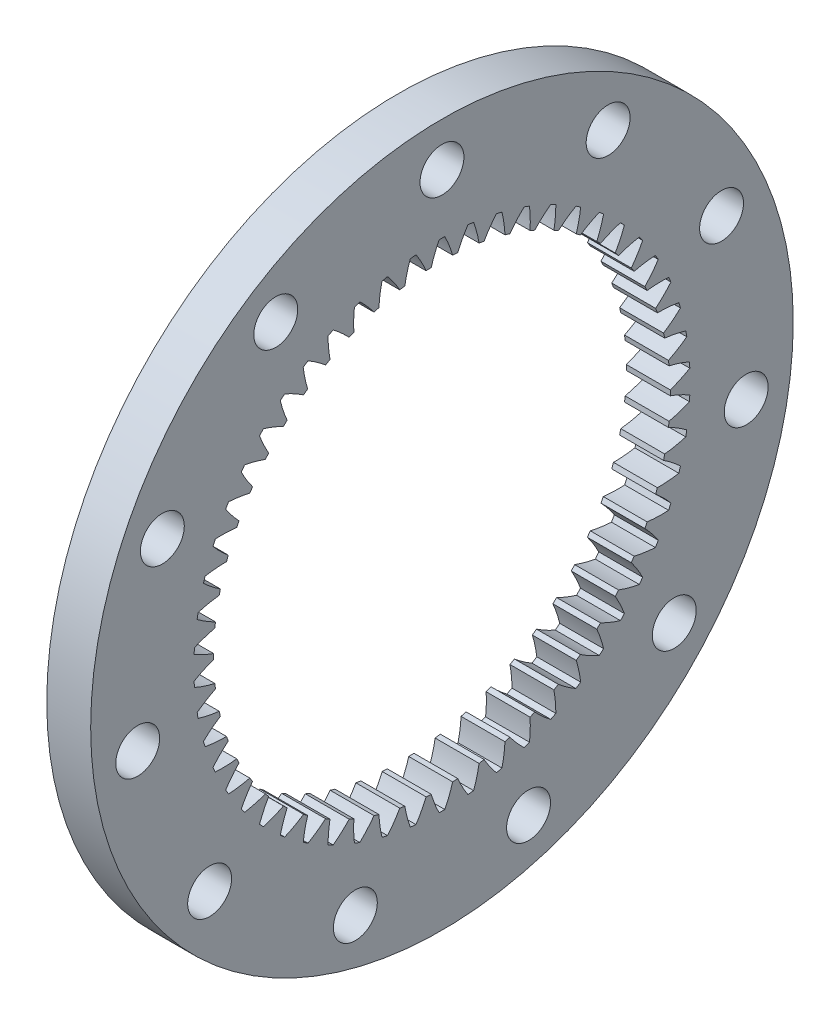
SolidWorks part; units mm, degrees
material "Nylon 101"
ref_plane "Plane1" through (0, 0, 0) normal (0, 0, 1) x (1, 0, 0)
ref_plane "Plane2" through (0, 0, 0) normal (0, 1, 0) x (1, 0, 0)
ref_plane "Plane3" through (0, 0, 0) normal (1, 0, 0) x (0, 0, -1)
sketch "HoldingSke" plane through (0, 0, 0) normal (0, 1, 0) x (1, 0, 0)
  line L0 (0, 0) -> (0.5878, -0.809)
  line L1 (-15, 0) -> (100, 0) construction
  line L2 (0, 0) -> (-2.1039, 2.3779)
  line L3 (0, 0) -> (-11.863, 4.5341)
  line L4 (0, 0) -> (5.0761, 6.9867)
  line L5 (0, 0) -> (-23.7986, -8.8762)
  line L6 (0, 0) -> (-10.5278, -7.1032)
  line L7 (-2.1039, 2.3779) -> (3.3635, 27.1825)
  line L8 (-76.2, 3.3779) -> (-54.61, 3.3779)
  line L9 (-71.009, 38.7566) -> (-53.1078, 45.2721)
  line L10 (-76.2, 71.12) -> (104.1128, 71.12)
  line L11 (0, 0) -> (-5, 0)
  line L12 (-76.2, 101.6) -> (-76.162, 101.6)
  line L13 (24.9733, 27.94) -> (52.9518, 28.4284)
  line L14 (24.9733, 27.94) -> (24.9743, 27.94)
  line L15 (24.9733, 27.94) -> (100.4006, 29.5858)
  circle A0 centre (0, 0) radius 40
  circle A1 centre (0, 0) radius 12.7
  circle A2 centre (0, 0) radius 12.7
  dimension "Num_teeth" = 54
  dimension "Pitch_radius" = 180.3128
  dimension "Width" = 5
  dimension "Diameter" = 80
sketch "BasProSke" plane through (0, 0, 0) normal (0, 1, 0) x (1, 0, 0)
  line L0 (-10, 0) -> (60, 0) construction
  line L1 (0, 26) -> (0, 40)
  line L2 (0, 26) -> (5, 26)
  line L3 (5, 26) -> (5, 40)
  line L4 (5, 40) -> (0, 40)
  dimension "Thickness" = 5
  dimension "Diameter" = 80
revolve "Base-Revolve" add sketch "BasProSke" angle 360 about L0
sketch "TooCutSke" plane through (0, 0, 0) normal (1, 0, 0) x (0, 0, -1)
  line L3 (0.8803, 26.9856) -> (0.8803, 53.6633) construction
  line L4 (0, 0) -> (0, 59.563) construction
  line L5 (0, 0) -> (-3.9729, 68.2119) construction
  line L6 (-11.739, 22.1895) -> (36.4511, 24.9963) construction
  circle A0 centre (0, 0) radius 27 construction
  circle A1 centre (0, 0) radius 28.251 construction
  circle A2 centre (0, 0) radius 22.8345 construction
  circle A3 centre (0, 0) radius 25.9746 construction
  arc A4 (1.2279, 25.9456) -> (0.3246, 28.2491) centre (-11.739, 22.1895) ccw
  arc A5 (1.2279, 25.9456) -> (-1.2279, 25.9456) centre (0, 0) ccw
  arc A6 (0.3246, 28.2491) -> (-0.3246, 28.2491) centre (0, 0) ccw
  arc A7 (-0.3246, 28.2491) -> (-1.2279, 25.9456) centre (11.739, 22.1895) ccw
extrude "ToothCut" cut sketch "TooCutSke" along normal through all
fillet "Breaks" [suppressed] radius 0.1
fillet "RootFillets" [suppressed] radius 0.251
pattern_circular "TeethCuts" count 54 every 6.667 about axis through (-10, 0, 0) along (1, 0, 0) of "RootFillets", "Breaks", "ToothCut"
sketch "Sketch1" plane through (5, 0, 0) normal (1, 0, 0) x (0, 0, -1)
  circle A0 centre (0, 0) radius 35 construction
  circle A1 centre (0, 35) radius 2.5
  circle A2 centre (18.9224, 29.4439) radius 2.5
  circle A3 centre (31.8371, 14.5395) radius 2.5
  circle A4 centre (34.6438, -4.981) radius 2.5
  circle A5 centre (26.4512, -22.9201) radius 2.5
  circle A6 centre (9.8606, -33.5823) radius 2.5
  circle A7 centre (-9.8606, -33.5823) radius 2.5
  circle A8 centre (-26.4512, -22.9201) radius 2.5
  circle A9 centre (-34.6438, -4.981) radius 2.5
  circle A10 centre (-31.8371, 14.5395) radius 2.5
  circle A11 centre (-18.9224, 29.4439) radius 2.5
  point P28 (0, 0)
  dimension "D1" = 70
  dimension "D2" = 5
  dimension "D3" = 11
extrude "Cut-Extrude1" cut sketch "Sketch1" against normal blind 10
equation "' \"Module@HoldingSke\" = 6.35"
equation "' \"Num_teeth@HoldingSke\" = 24"
equation "' \"Ap@HoldingSke\" =  14.5"
equation "' \"Ap@HoldingSke\" = 14.5"
equation "' \"Width@HoldingSke\" = 12"
equation "' \"Diameter@HoldingSke\" = 8 * 25.4"
equation "' \"Show_teeth@HoldingSke\" = 100"
equation "' \"Backlash@HoldingSke\" = 0.009 * 25.4"
equation "' \"Addendum_fac@HoldingSke\" = 1.0"
equation "' \"Dedendum_fac@HoldingSke\" = 1.25"
equation "' \"Dedendum_add@HoldingSke\" = 0.00005 * 25.4"
equation "' \"Clearance_fac@HoldingSke\" = 0.25"
equation "\"Pitch@HoldingSke\" = 1 / \"Module@HoldingSke\" "
equation "\"Overcut_dia@TooCutSke\" = (\"Num_teeth@HoldingSke\" - 2 * \"Addendum_fac@HoldingSke\") / \"Pitch@HoldingSke\" - 0.002 * 25.4"
equation "\"Pitch_dia@TooCutSke\" = \"Num_teeth@HoldingSke\" / \"Pitch@HoldingSke\""
equation "\"Base_dia@TooCutSke\" = \"Num_teeth@HoldingSke\" / \"Pitch@HoldingSke\" * cos((\"Ap@HoldingSke\"  * 3.14159265 / 180)) * 0.90"
equation "\"Root_dia@TooCutSke\" = \"Num_teeth@HoldingSke\"  / \"Pitch@HoldingSke\" + 2 *  \"Dedendum_fac@HoldingSke\"/ \"Pitch@HoldingSke\" + \"Dedendum_add@HoldingSke\" * 2"
equation "\"Half_ang@TooCutSke\" = 180 / \"Num_teeth@HoldingSke\""
equation "\"Half_CT@TooCutSke\" = \"Num_teeth@HoldingSke\" / \"Pitch@HoldingSke\" * sin((3.14159265 / 2 / \"Num_teeth@HoldingSke\")) / 2 + 10 * \"Backlash@HoldingSke\" / 4"
equation "\"Flank_rad@TooCutSke\" = \"Num_teeth@HoldingSke\" / \"Pitch@HoldingSke\" / 4"
equation "\"Radius@RootFillets\"= \"Clearance_fac@HoldingSke\" / \"Pitch@HoldingSke\" + \"Dedendum_add@HoldingSke\""
equation "\"Break_rad@Breaks\" = 0.02 / \"Pitch@HoldingSke\" * 5"
equation "\"Num_teeth@TeethCuts\" = int( \"Show_teeth@HoldingSke\" ) + 1"
equation "\"Num_teeth@TeethCuts\" = ((sgn( \"Num_teeth@TeethCuts\" - \"Num_teeth@HoldingSke\" )-1)*( \"Num_teeth@TeethCuts\" - \"Num_teeth@HoldingSke\" ))/-2+ \"Num_teeth@HoldingSke\""
equation "\"Num_teeth@TeethCuts\" = ((sgn( \"Num_teeth@TeethCuts\" - 2.0)+1)*( \"Num_teeth@TeethCuts\" - 2.0))/2 +2.0"
equation "\"Angle@TeethCuts\" = 360.0 / \"Num_teeth@HoldingSke\""
equation "\"Diameter@BasProSke\" = \"Num_teeth@HoldingSke\"  / \"Pitch@HoldingSke\" + 2 *  \"Dedendum_fac@HoldingSke\"/ \"Pitch@HoldingSke\" + \"Dedendum_add@HoldingSke\" * 2 + 0.002 * 25.4"
equation "\"Diameter@BasProSke\" = ((sgn( \"Diameter@BasProSke\"  - \"Diameter@HoldingSke\" )+1)*( \"Diameter@BasProSke\"  - \"Diameter@HoldingSke\" ))/2 + \"Diameter@HoldingSke\""
equation "\"Inside_diameter@BasProSke\" =  (\"Num_teeth@HoldingSke\" - 2 * \"Addendum_fac@HoldingSke\") / \"Pitch@HoldingSke\" "
equation "\"Thickness@BasProSke\"  = \"Width@HoldingSke\""
